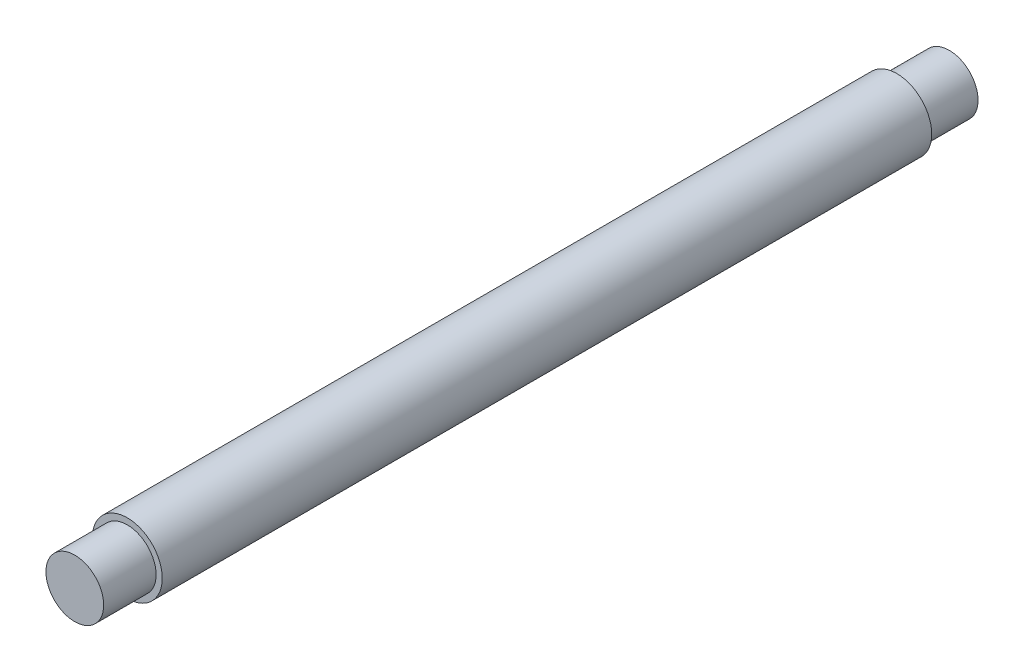
SolidWorks part; units mm, degrees
material "Cast Stainless Steel"
ref_plane "Front Plane" through (0, 0, 0) normal (0, 0, 1) x (1, 0, 0)
ref_plane "Top Plane" through (0, 0, 0) normal (0, 1, 0) x (1, 0, 0)
ref_plane "Right Plane" through (0, 0, 0) normal (1, 0, 0) x (0, 0, -1)
sketch "Sketch2" plane through (0, 0, 0) normal (0, 0, 1) x (1, 0, 0)
  circle A0 centre (0, 0) radius 20
  dimension "D1" = 40
extrude "Boss-Extrude1" add sketch "Sketch2" along normal blind 220 and the other way blind 220
sketch "Sketch3" plane through (0, 0, 220) normal (0, 0, 1) x (1, 0, 0)
  circle A0 centre (0, 0) radius 16.5
  dimension "D1" = 33
extrude "Boss-Extrude2" add sketch "Sketch3" along normal blind 30
sketch "Sketch4" plane through (0, 0, -220) normal (0, 0, -1) x (-1, 0, 0)
  circle A0 centre (0, 0) radius 16.5
  dimension "D1" = 33
extrude "Boss-Extrude3" add sketch "Sketch4" along normal blind 30
